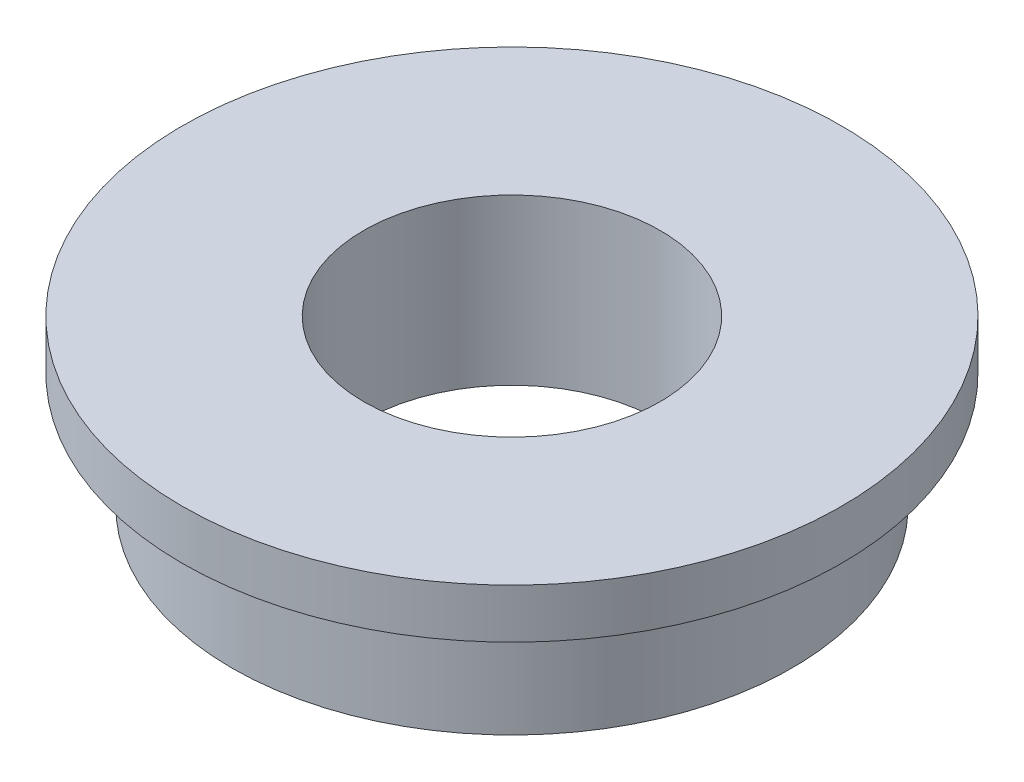
SolidWorks part; units mm, degrees
ref_plane "Front Plane" through (0, 0, 0) normal (0, 0, 1) x (1, 0, 0)
ref_plane "Top Plane" through (0, 0, 0) normal (0, 1, 0) x (1, 0, 0)
ref_plane "Right Plane" through (0, 0, 0) normal (1, 0, 0) x (0, 0, -1)
sketch "Sketch2" plane through (0, 0, 0) normal (0, 1, 0) x (1, 0, 0)
  circle A0 centre (0, 0) radius 4.5
  circle A1 centre (0, 0) radius 8.5
  dimension "D1" = 9
  dimension "D2" = 17
extrude "Boss-Extrude1" add sketch "Sketch2" along normal blind 5
sketch "Sketch3" plane through (0, 5, 0) normal (0, 1, 0) x (1, 0, 0)
  circle A0 centre (0, 0) radius 10
  circle A1 centre (0, 0) radius 8.5 construction
  circle A2 centre (0, 0) radius 8.5
  dimension "D1" = 1.5
extrude "Boss-Extrude2" add sketch "Sketch3" against normal blind 1.5
